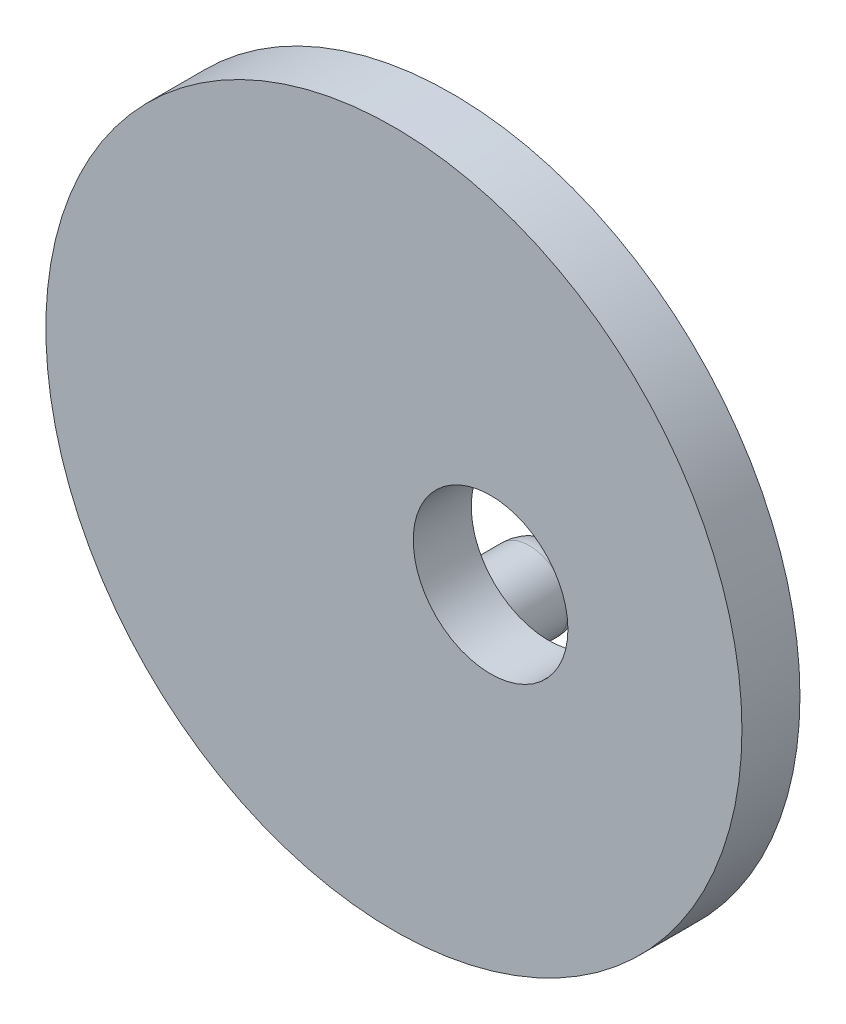
SolidWorks part; units mm, degrees
material "聚脂树脂"
ref_plane "前视基准面" through (0, 0, 0) normal (0, 0, 1) x (1, 0, 0)
ref_plane "上视基准面" through (0, 0, 0) normal (0, 1, 0) x (1, 0, 0)
ref_plane "右视基准面" through (0, 0, 0) normal (1, 0, 0) x (0, 0, -1)
other "Configuration Table"
sketch "草图2" plane through (0, 0, 0) normal (0, 0, 1) x (1, 0, 0)
  circle A0 centre (-0.0015, -3.1237) radius 1 construction
  circle A2 centre (0, 0) radius 9
  circle A3 centre (-0.0015, 3.1237) radius 1 construction
  circle A8 centre (2.5, 0) radius 2 construction
  circle A9 centre (-0.0015, -3.1237) radius 1
  circle A10 centre (-0.0015, 3.1237) radius 1
  circle A11 centre (2.5, 0) radius 2
extrude "凸台-拉伸1" add sketch "草图2" along normal blind 1.5 contours A2 A11 A10 A9 | A9 | A10 region at (-0.1333, 0, 0) region at (-0.0015, -3.1237, 0) region at (-0.0015, 3.1237, 0)
extrude "凸台-拉伸3" add sketch "草图2<3>" against normal blind 3 contours A9 | A10 region at (-0.0015, -3.1237, 0) region at (-0.0015, 3.1237, 0)
sketch "草图2<3>" plane through (0, 0, 0) normal (0, 0, 1) x (1, 0, 0) same geometry as "草图2"
fillet "圆角1" radius 1 2 edges at (0.9985, -3.1237, -3) (0.9985, 3.1237, -3)
